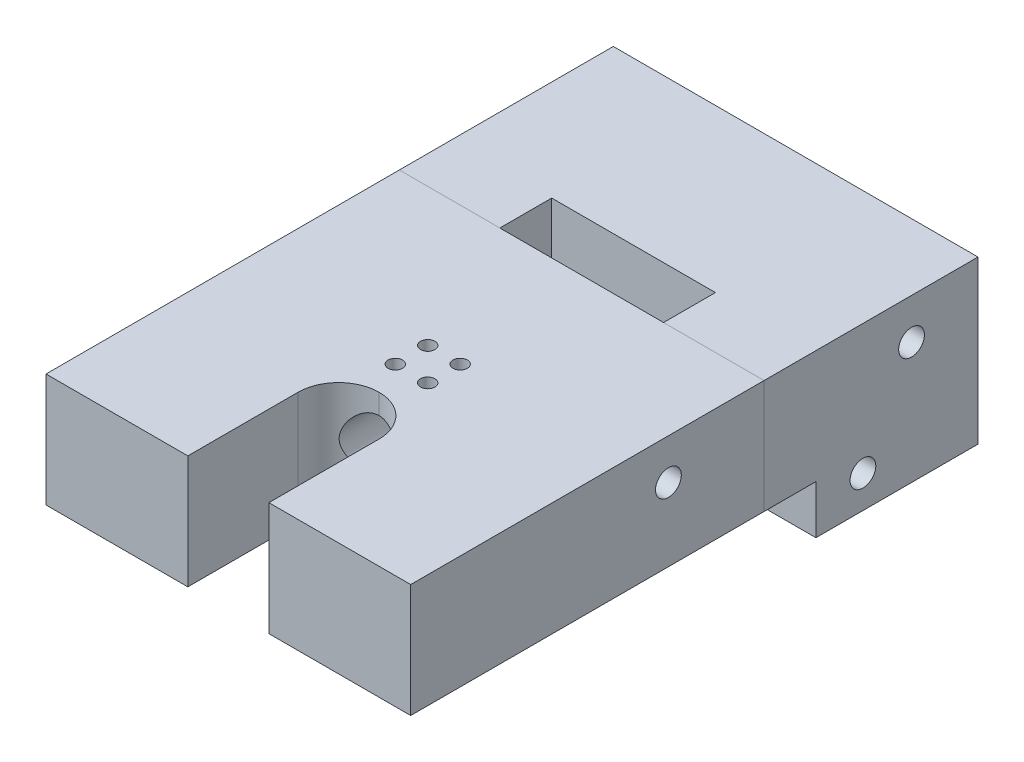
SolidWorks part; units mm, degrees
material "Nylon 6/10"
ref_plane "Front Plane" through (0, 0, 0) normal (0, 0, 1) x (1, 0, 0)
ref_plane "Top Plane" through (0, 0, 0) normal (0, 1, 0) x (1, 0, 0)
ref_plane "Right Plane" through (0, 0, 0) normal (1, 0, 0) x (0, 0, -1)
sketch "Sketch1" plane through (0, 0, 0) normal (0, 1, 0) x (1, 0, 0)
  line L1 (-28.575, -44.45) -> (28.575, -44.45)
  line L2 (-28.575, -44.45) -> (-28.575, 44.45)
  line L3 (-28.575, 44.45) -> (28.575, 44.45)
  line L4 (28.575, -44.45) -> (28.575, 44.45)
  line L5 (-28.575, -44.45) -> (28.575, 44.45) construction
  line L6 (-28.575, 44.45) -> (28.575, -44.45) construction
  point P0 (0, 0)
  dimension "D1" = 57.15
  dimension "D2" = 88.9
extrude "Base" add sketch "Sketch1" along normal blind 12.7 and the other way blind 12.7
sketch "Sketch2" plane through (0, 0, -44.45) normal (0, 0, -1) x (-1, 0, 0)
  line L1 (-28.575, -12.7) -> (28.575, -12.7) construction
  circle A0 centre (0, -12.7) radius 4.7625
  dimension "D1" = 9.525
extrude "ShaftGuide" cut sketch "Sketch2" against normal blind 25.4
ref_plane "Plane1" through (0, -12.7, 0) normal (0, -1, 0) x (-1, 0, 0)
sketch "Sketch3" plane through (0, -12.7, 0) normal (0, -1, 0) x (-1, 0, 0)
  line L0 (10.922, -20.828) -> (16.002, -20.828)
  line L1 (28.575, -44.45) -> (-28.575, -44.45) construction
  line L2 (-28.575, -44.45) -> (-28.575, 44.45) construction
  line L3 (0, 0) -> (0, 102.0916) construction
  line L4 (-10.922, -20.828) -> (-16.002, -20.828)
  line L5 (-10.922, -20.828) -> (-10.922, 10.922)
  line L6 (-28.575, -44.45) -> (28.575, -44.45)
  line L7 (-10.922, 10.922) -> (10.922, 10.922)
  line L8 (10.922, -20.828) -> (10.922, 10.922)
  line L9 (-16.002, -20.828) -> (-16.002, 10.922)
  line L10 (-16.002, 10.922) -> (-28.575, 10.922)
  line L11 (-28.575, -44.45) -> (-28.575, -3.175)
  line L12 (-28.575, 10.922) -> (-28.575, -3.175)
  line L13 (28.575, -44.45) -> (28.575, -3.175)
  line L14 (4.7625, 44.45) -> (4.7625, 19.05)
  line L15 (4.7625, 19.05) -> (-4.7625, 19.05)
  line L16 (-4.7625, 19.05) -> (-4.7625, 44.45)
  line L17 (-4.7625, 44.45) -> (-28.575, 44.45)
  line L18 (-28.575, 44.45) -> (-28.575, -44.45)
  line L19 (-28.575, -44.45) -> (28.575, -44.45)
  line L20 (28.575, -44.45) -> (28.575, 44.45)
  line L21 (28.575, 44.45) -> (4.7625, 44.45)
  line L22 (16.002, -20.828) -> (16.002, 10.922)
  line L23 (16.002, 10.922) -> (28.575, 10.922)
  line L24 (28.575, 10.922) -> (28.575, -3.175)
  line L25 (-4.7625, 44.45) -> (-28.575, 44.45) construction
  line L28 (28.575, -44.45) -> (28.575, 44.45) construction
  line L29 (28.575, 44.45) -> (4.7625, 44.45) construction
  dimension "D6" = 21.844
  dimension "D9" = 31.75
  dimension "D2" = 5.08
  dimension "D3" = 33.528
  dimension "D1" = 0
extrude "ActuatorPlaneCut" cut sketch "Sketch3" against normal blind 7.62
sketch "Sketch5" plane through (0, 0, 0) normal (0, 1, 0) x (1, 0, 0)
  line L0 (-4.7625, 44.45) -> (-28.575, 44.45) construction
  line L1 (12.827, 19.05) -> (-12.827, 19.05)
  line L2 (12.827, 10.922) -> (12.827, 19.05)
  line L3 (12.827, 10.922) -> (-12.827, 10.922)
  line L4 (0, 0) -> (0, 121.8983) construction
  line L6 (-12.827, 10.922) -> (-12.827, 19.05)
  point P17 (12.827, 10.922)
  point P20 (12.827, 19.05)
  dimension "D1" = 8.128
  dimension "D2" = 25.654
  dimension "D4" = 25.4
extrude "WireChannel" cut sketch "Sketch5" along normal through all and the other way through all
ref_plane "Plane3" through (0, -5.08, 0) normal (0, -1, 0) x (-1, 0, 0)
sketch "Sketch13" plane through (0, -12.7, 0) normal (0, -1, 0) x (1, 0, 0)
  line L0 (28.575, -10.922) -> (28.575, -44.45) construction
  line L1 (12.827, -10.922) -> (28.575, -10.922)
  line L2 (12.827, -10.922) -> (12.827, -19.05)
  line L3 (12.827, -19.05) -> (28.575, -19.05)
  line L4 (28.575, -10.922) -> (28.575, -19.05)
  line L5 (12.827, -19.05) -> (4.7625, -19.05) construction
extrude "WireChannelBottom" cut sketch "Sketch13" against normal blind 7.62
ref_plane "Plane4" through (0, 0, -10.922) normal (0, 0, -1) x (-1, 0, 0)
sketch "Sketch15" plane through (0, 0, -44.45) normal (0, 0, -1) x (-1, 0, 0)
  line L0 (-28.575, 0) -> (28.575, 0) construction
  line L1 (-28.575, -12.7) -> (-28.575, 12.7) construction
  line L2 (28.575, -12.7) -> (28.575, 12.7) construction
  circle A0 centre (-14.605, 0) radius 2.0193
  circle A1 centre (14.605, 0) radius 2.0193
  dimension "D1" = 4.0386
  dimension "D3" = 13.97
  dimension "D2" = 13.97
extrude "FrontBoltHoles" cut sketch "Sketch15" against normal blind 57.15
sketch "Sketch17" plane through (0, 0, -44.45) normal (0, 0, -1) x (-1, 0, 0)
  line L0 (-38.1, 0) -> (28.575, 0) construction
  line L3 (28.575, -12.7) -> (28.575, 12.7) construction
  circle A0 centre (-14.605, 0) radius 4.2164
  circle A1 centre (14.605, 0) radius 4.2164
  circle A3 centre (14.605, 0) radius 2.0193 construction
  circle A4 centre (-14.605, 0) radius 2.0193 construction
  dimension "D1" = 8.4328
extrude "FrontCounterBores" cut sketch "Sketch17" against normal blind 5.461
sketch "Sketch19" plane through (0, -12.7, 0) normal (0, -1, 0) x (1, 0, 0)
  line L0 (-4.7625, -44.45) -> (4.7625, -44.45) construction
  line L1 (-4.7625, -44.45) -> (-28.575, -44.45) construction
  line L3 (0, 0) -> (0, -47.7058) construction
  circle A0 centre (-12.7, -28.575) radius 1.8288
  circle A1 centre (12.7, -28.575) radius 1.8288
  point P2 (0, -44.45)
  dimension "D1" = 3.6576
  dimension "D2" = 15.875
  dimension "D4" = 12.7
sketch "Sketch40" plane through (0, -12.7, 0) normal (0, -1, 0) x (1, 0, 0)
  line L1 (10.922, -10.922) -> (-10.922, -10.922)
  line L2 (10.922, -10.922) -> (10.922, 17.653)
  line L3 (7.747, 20.828) -> (-7.747, 20.828)
  line L4 (-10.922, -10.922) -> (-10.922, 17.653)
  arc A0 (-7.747, 20.828) -> (-10.922, 17.653) centre (-7.747, 17.653) ccw
  arc A1 (7.747, 20.828) -> (10.922, 17.653) centre (7.747, 17.653) cw
  point P8 (-10.922, 20.828)
  dimension "D1" = 3.175
extrude "GearBoxPit" cut sketch "Sketch40" against normal blind 11.176
sketch "Sketch22" plane through (0, -12.7, 0) normal (0, -1, 0) x (1, 0, 0)
  line L0 (2.413, 19.1929) -> (-2.413, 19.1929) construction
  line L1 (2.413, 8.5249) -> (-2.413, 8.5249) construction
  line L2 (2.413, 19.5898) -> (-2.413, 19.5898)
  line L3 (2.413, 18.796) -> (-2.413, 18.796)
  line L4 (2.413, 8.128) -> (-2.413, 8.128)
  line L5 (2.413, 8.9218) -> (-2.413, 8.9218)
  line L6 (0, -39.4682) -> (0, -19.7785) construction
  line L7 (10.922, 13.8589) -> (-10.922, 13.8589) construction
  line L8 (10.922, -10.922) -> (10.922, 20.828) construction
  line L9 (-10.922, 20.828) -> (-10.922, -10.922) construction
  line L11 (-10.922, -10.922) -> (10.922, -10.922) construction
  arc A0 (2.413, 8.128) -> (2.413, 8.9218) centre (2.413, 8.5249) ccw
  arc A1 (-2.413, 8.9218) -> (-2.413, 8.128) centre (-2.413, 8.5249) ccw
  arc A2 (2.413, 19.5898) -> (2.413, 18.796) centre (2.413, 19.1929) cw
  arc A3 (-2.413, 18.796) -> (-2.413, 19.5898) centre (-2.413, 19.1929) cw
  point P6 (0, 8.5249)
  point P17 (0, 19.1929)
  dimension "D1" = 0.7937
  dimension "D2" = 4.826
  dimension "D3" = 10.668
  dimension "D4" = 19.05
extrude "GearBoxSlots" cut sketch "Sketch22" against normal blind 13.716
hole_wizard "ToggleAssemHoles" positions "Sketch50" profile "Sketch49" tap size "#6-32" standard "ANSI Inch"
sketch "Sketch50" plane through (0, -12.7, 0) normal (0, -1, 0) x (-1, 0, 0)
  line L0 (-28.575, 44.45) -> (-4.7625, 44.45) construction
  line L1 (4.7625, 44.45) -> (-4.7625, 44.45) construction
  line L2 (0, 0) -> (0, 53.5676) construction
  point P0 (12.7, 28.575)
  point P2 (-12.7, 28.575)
  point P8 (0, 44.45)
  dimension "D1" = 15.875
  dimension "D2" = 12.7
sketch "Sketch49" plane through (-12.7, -12.7, -28.575) normal (1, 0, 0) x (0, 0, -1)
  line L0 (0, 0) -> (0, 10.2107)
  line L1 (0, 10.2107) -> (1.3525, 9.398)
  line L2 (1.3525, 9.398) -> (1.3525, 0)
  line L5 (1.3525, 0) -> (0, 0)
  line L10 (0, 10.2107) -> (-1.3526, 9.398) construction
  line L11 (0, -6.35) -> (0, 107.95) construction
  dimension "Tap Drill Dia." = 2.7051
  dimension "Tap Drill Depth" = 9.398
  dimension "Drill Angle" = 118
cosmetic thread "Hole Thread12" parameters "D1"=9.398, "D2"=3.5052
cosmetic thread "Hole Thread13" parameters "D1"=9.398, "D2"=3.5052
sketch "Sketch25" plane through (28.575, 0, 0) normal (1, 0, 0) x (0, 0, -1)
  line L0 (-44.45, 12.7) -> (44.45, 12.7) construction
  line L1 (44.45, -12.7) -> (44.45, 12.7) construction
  point P0 (34.036, 6.35)
  point P1 (26.416, -7.62)
  point P2 (-4.064, 6.35)
  dimension "D1" = 7.62
  dimension "D2" = 13.97
  dimension "D3" = 38.1
  dimension "D4" = 6.35
  dimension "D5" = 10.414
hole_wizard "PitchAssemHoles" positions "Sketch29" profile "Sketch28" tap size "#10-32" standard "ANSI Inch"
sketch "Sketch29" plane through (28.575, 0, 0) normal (1, 0, 0) x (0, 0, -1)
  point P0 (34.036, 6.35)
  point P3 (26.416, -7.62)
  point P6 (-4.064, 6.35)
sketch "Sketch28" plane through (28.575, 6.35, -34.036) normal (0, 1, 0) x (0, 0, -1)
  line L0 (0, 0) -> (0, 15.3357)
  line L1 (0, 15.3357) -> (2.0193, 14.1224)
  line L2 (2.0193, 14.1224) -> (2.0193, 0)
  line L5 (2.0193, 0) -> (0, 0)
  line L10 (0, 15.3357) -> (-2.0193, 14.1224) construction
  line L11 (0, -6.35) -> (0, 107.95) construction
  dimension "Tap Drill Dia." = 4.0386
  dimension "Tap Drill Depth" = 14.1224
  dimension "Drill Angle" = 118
cosmetic thread "Hole Thread3" parameters "D1"=10.16, "D2"=4.826
cosmetic thread "Hole Thread4" parameters "D1"=10.16, "D2"=4.826
cosmetic thread "Hole Thread5" parameters "D1"=10.16, "D2"=4.826
sketch "Sketch39" plane through (0, 12.7, 0) normal (0, 1, 0) x (1, 0, 0)
  line L0 (7.747, -20.828) -> (-7.747, -20.828) construction
  line L1 (-6.35, -97.028) -> (6.35, -97.028)
  line L2 (-6.35, -97.028) -> (-6.35, -27.1755)
  line L3 (-0.0025, -20.828) -> (0.0025, -20.828)
  line L4 (6.35, -97.028) -> (6.35, -27.1755)
  line L5 (-6.35, -97.028) -> (6.35, -20.828) construction
  line L6 (-6.35, -20.828) -> (6.35, -97.028) construction
  arc A0 (0.0025, -20.828) -> (6.35, -27.1755) centre (0.0025, -27.1755) cw
  arc A1 (-6.35, -27.1755) -> (-0.0025, -20.828) centre (-0.0025, -27.1755) cw
  point P0 (0, -58.928)
  point P7 (0, 0)
  dimension "D3" = 6.3475
  dimension "D1" = 12.7
  dimension "D2" = 76.2
extrude "GripSlot" cut sketch "Sketch39" against normal blind 18.288
sketch "Sketch51" plane through (0, 0, 44.45) normal (0, 0, -1) x (-1, 0, 0)
  line L0 (12.827, 12.7) -> (-12.827, 12.7) construction
  circle A0 centre (0, 5.08) radius 4.445
  dimension "D2" = 8.89
  dimension "D1" = 7.62
extrude "LinActHole" cut sketch "Sketch51" along normal up to surface (36.322 mm away) up to face at (0, -0.254, 8.128)
hole_wizard "LinActSetHoles" positions "Sketch54" profile "Sketch53" tap size "#4-40" standard "ANSI Inch" end condition up to next
sketch "Sketch54" plane through (0, 12.7, 0) normal (0, 1, 0) x (1, 0, 0)
  line L0 (0, 0) -> (0, -17.2208) construction
  point P0 (2.54, -15.748)
  point P2 (-2.54, -15.748)
  point P4 (2.54, -10.668)
  point P6 (-2.54, -10.668)
  dimension "D1" = 5.08
  dimension "D2" = 5.08
  dimension "D3" = 5.08
sketch "Sketch53" plane through (2.54, 12.7, 15.748) normal (1, 0, 0) x (0, 0, 1)
  line L0 (0, 0) -> (0, 3.9722)
  line L1 (0, 3.9722) -> (1.1303, 3.9722)
  line L2 (1.1303, 3.9722) -> (1.1303, 0)
  line L5 (1.1303, 0) -> (0, 0)
  line L11 (0, -6.35) -> (0, 107.95) construction
  dimension "Thru Tap Drill Dia." = 2.2606
  dimension "Thru Tap Drill Depth" = 3.9722
cosmetic thread "Hole Thread14" parameters "D2"=2.8448
cosmetic thread "Hole Thread15" parameters "D2"=2.8448
cosmetic thread "Hole Thread16" parameters "D2"=2.8448
cosmetic thread "Hole Thread17" parameters "D2"=2.8448
sketch "Sketch44" [suppressed] plane through (0, 12.7, 0) normal (0, 1, 0) x (1, 0, 0)
  line L0 (28.575, -12.7) -> (28.575, -50.8)
  line L1 (19.05, -50.8) -> (19.05, -22.225)
  line L2 (6.35, -50.8) -> (28.575, -50.8) construction
  line L3 (28.575, -50.8) -> (28.575, 50.8) construction
  line L4 (28.575, -50.8) -> (19.05, -50.8)
  line L5 (0, 0) -> (0, -86.719) construction
  line L6 (-28.575, -50.8) -> (-19.05, -50.8)
  line L7 (-19.05, -50.8) -> (-19.05, -22.225)
  line L8 (-28.575, -12.7) -> (-28.575, -50.8)
  line L9 (-28.575, 50.8) -> (-28.575, -50.8) construction
  line L10 (28.575, 25.4) -> (28.575, -50.8) construction
  arc A0 (28.575, -12.7) -> (19.05, -22.225) centre (28.575, -22.225) ccw
  arc A1 (-28.575, -12.7) -> (-19.05, -22.225) centre (-28.575, -22.225) cw
  dimension "D2" = 38.1
  dimension "D3" = 9.525
extrude "RoundCutAways" [suppressed] cut sketch "Sketch44" against normal through all
chamfer "Chamfer1" [suppressed] distance 6.35 angle 45
split "Split1" trim tools "Plane4" bodies to split 144 resulting bodies 124 125
